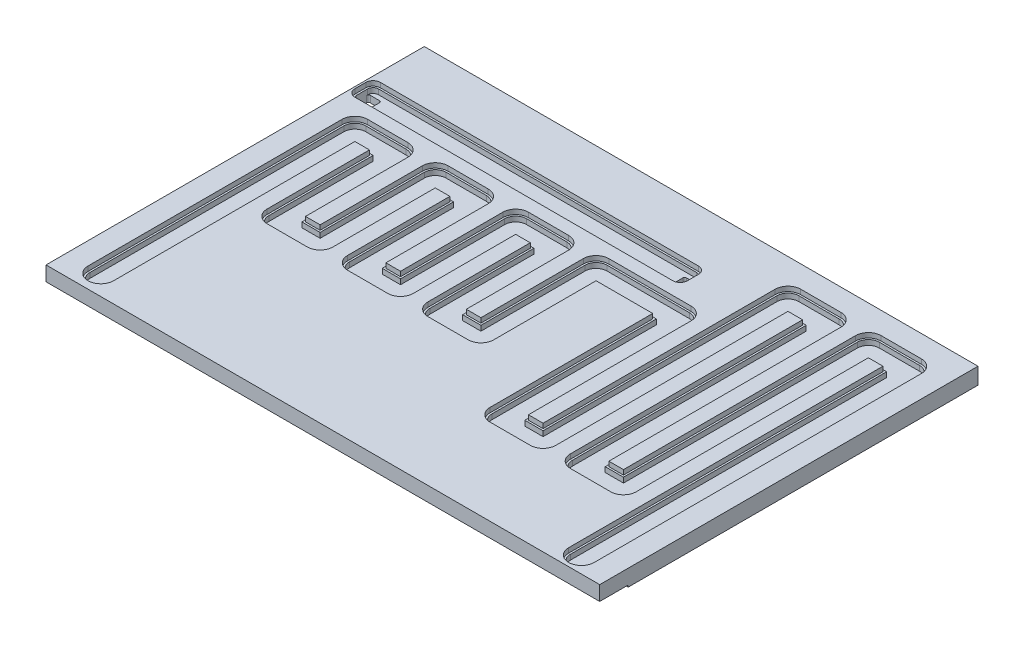
SolidWorks part; units mm, degrees
ref_plane "前视基准面" through (0, 0, 0) normal (0, 0, 1) x (1, 0, 0)
ref_plane "上视基准面" through (0, 0, 0) normal (0, 1, 0) x (1, 0, 0)
ref_plane "右视基准面" through (0, 0, 0) normal (1, 0, 0) x (0, 0, -1)
sketch "草图1" plane through (0, 0, 0) normal (0, 1, 0) x (1, 0, 0)
  line L0 (5, -195) -> (5, -165)
  line L1 (0, 0) -> (1515, 0)
  line L2 (0, 0) -> (0, -1035)
  line L3 (0, -1035) -> (1515, -1035)
  line L4 (1515, 0) -> (1515, -1035)
  line L5 (25, -145) -> (895, -145)
  line L6 (915, -165) -> (915, -195)
  line L7 (895, -215) -> (25, -215)
  line L8 (-125.9274, -180) -> (1036.3031, -180) construction
  line L9 (25, -150) -> (895, -150)
  line L10 (910, -165) -> (910, -195)
  line L11 (895, -210) -> (25, -210)
  line L12 (10, -195) -> (10, -165)
  line L13 (60, -980) -> (60, -285)
  line L14 (40, -197.5) -> (15, -197.5)
  line L15 (45, -192.5) -> (45, -167.5)
  line L16 (40, -162.5) -> (15, -162.5)
  line L17 (10, -192.5) -> (10, -167.5)
  line L18 (45, -197.5) -> (10, -162.5) construction
  line L19 (45, -162.5) -> (10, -197.5) construction
  line L20 (905, -197.5) -> (880, -197.5)
  line L21 (910, -192.5) -> (910, -167.5)
  line L22 (905, -162.5) -> (880, -162.5)
  line L23 (875, -192.5) -> (875, -167.5)
  line L24 (910, -197.5) -> (875, -162.5) construction
  line L25 (910, -162.5) -> (875, -197.5) construction
  line L26 (95, -250) -> (205, -250)
  line L27 (240, -285) -> (240, -565)
  line L28 (240, -565) -> (280, -565)
  line L29 (280, -565) -> (280, -285)
  line L30 (315, -250) -> (425, -250)
  line L31 (460, -285) -> (460, -565)
  line L32 (460, -565) -> (500, -565)
  line L33 (500, -565) -> (500, -285)
  line L34 (535, -250) -> (645, -250)
  line L35 (680, -285) -> (680, -565)
  line L36 (680, -565) -> (720, -565)
  line L37 (720, -565) -> (720, -285)
  line L38 (755, -250) -> (980, -250)
  line L39 (1015, -285) -> (1015, -730)
  line L40 (1015, -730) -> (1055, -730)
  line L41 (1055, -730) -> (1055, -95)
  line L42 (1090, -60) -> (1200, -60)
  line L43 (1235, -95) -> (1235, -730)
  line L44 (1235, -730) -> (1275, -730)
  line L45 (1275, -730) -> (1275, -95)
  line L46 (1310, -60) -> (1420, -60)
  line L47 (1455, -95) -> (1455, -990)
  line L48 (1455, -990) -> (1385, -990) construction
  line L49 (1385, -990) -> (1385, -130)
  line L50 (1385, -130) -> (1345, -130)
  line L51 (1345, -130) -> (1345, -765)
  line L52 (1310, -800) -> (1200, -800)
  line L53 (1165, -765) -> (1165, -130)
  line L54 (1165, -130) -> (1125, -130)
  line L55 (1125, -130) -> (1125, -765)
  line L56 (1090, -800) -> (980, -800)
  line L57 (945, -765) -> (945, -320)
  line L58 (945, -320) -> (790, -320)
  line L59 (790, -320) -> (790, -600)
  line L60 (755, -635) -> (645, -635)
  line L61 (610, -600) -> (610, -320)
  line L62 (610, -320) -> (570, -320)
  line L63 (570, -320) -> (570, -600)
  line L64 (535, -635) -> (425, -635)
  line L65 (390, -600) -> (390, -320)
  line L66 (390, -320) -> (350, -320)
  line L67 (350, -320) -> (350, -600)
  line L68 (315, -635) -> (205, -635)
  line L69 (170, -600) -> (170, -320)
  line L70 (170, -320) -> (130, -320)
  line L71 (130, -320) -> (130, -980)
  line L72 (130, -980) -> (60, -980) construction
  line L73 (1390, -990) -> (1390, -125)
  line L74 (1390, -125) -> (1340, -125)
  line L75 (1340, -125) -> (1340, -765)
  line L76 (1310, -795) -> (1200, -795)
  line L77 (1170, -765) -> (1170, -125)
  line L78 (1170, -125) -> (1120, -125)
  line L79 (1120, -125) -> (1120, -765)
  line L80 (1090, -795) -> (980, -795)
  line L81 (950, -765) -> (950, -315)
  line L82 (950, -315) -> (785, -315)
  line L83 (785, -315) -> (785, -600)
  line L84 (755, -630) -> (645, -630)
  line L85 (615, -600) -> (615, -315)
  line L86 (615, -315) -> (565, -315)
  line L87 (565, -315) -> (565, -600)
  line L88 (535, -630) -> (425, -630)
  line L89 (395, -600) -> (395, -315)
  line L90 (395, -315) -> (345, -315)
  line L91 (345, -315) -> (345, -600)
  line L92 (315, -630) -> (205, -630)
  line L93 (175, -600) -> (175, -315)
  line L94 (175, -315) -> (125, -315)
  line L95 (125, -315) -> (125, -980)
  line L96 (65, -980) -> (65, -285)
  line L97 (95, -255) -> (205, -255)
  line L98 (235, -285) -> (235, -570)
  line L99 (235, -570) -> (285, -570)
  line L100 (285, -570) -> (285, -285)
  line L101 (315, -255) -> (425, -255)
  line L102 (455, -285) -> (455, -570)
  line L103 (455, -570) -> (505, -570)
  line L104 (505, -570) -> (505, -285)
  line L105 (535, -255) -> (645, -255)
  line L106 (675, -285) -> (675, -570)
  line L107 (675, -570) -> (725, -570)
  line L108 (725, -570) -> (725, -285)
  line L109 (755, -255) -> (980, -255)
  line L110 (1010, -285) -> (1010, -735)
  line L111 (1010, -735) -> (1060, -735)
  line L112 (1060, -735) -> (1060, -95)
  line L113 (1090, -65) -> (1200, -65)
  line L114 (1230, -95) -> (1230, -735)
  line L115 (1230, -735) -> (1280, -735)
  line L116 (1280, -735) -> (1280, -95)
  line L117 (1310, -65) -> (1420, -65)
  line L118 (1450, -95) -> (1450, -990)
  arc A0 (5, -195) -> (25, -215) centre (25, -195) ccw
  arc A1 (5, -165) -> (25, -145) centre (25, -165) cw
  arc A2 (915, -195) -> (895, -215) centre (895, -195) cw
  arc A3 (895, -145) -> (915, -165) centre (895, -165) cw
  arc A4 (895, -150) -> (910, -165) centre (895, -165) cw
  arc A5 (910, -195) -> (895, -210) centre (895, -195) cw
  arc A6 (10, -195) -> (25, -210) centre (25, -195) ccw
  arc A7 (10, -165) -> (25, -150) centre (25, -165) cw
  arc A10 (205, -635) -> (170, -600) centre (205, -600) cw
  arc A11 (350, -600) -> (315, -635) centre (315, -600) cw
  arc A12 (425, -635) -> (390, -600) centre (425, -600) cw
  arc A13 (570, -600) -> (535, -635) centre (535, -600) cw
  arc A14 (645, -635) -> (610, -600) centre (645, -600) cw
  arc A15 (790, -600) -> (755, -635) centre (755, -600) cw
  arc A16 (980, -800) -> (945, -765) centre (980, -765) cw
  arc A17 (1125, -765) -> (1090, -800) centre (1090, -765) cw
  arc A18 (1200, -800) -> (1165, -765) centre (1200, -765) cw
  arc A19 (1345, -765) -> (1310, -800) centre (1310, -765) cw
  arc A20 (1420, -60) -> (1455, -95) centre (1420, -95) cw
  arc A21 (1275, -95) -> (1310, -60) centre (1310, -95) cw
  arc A22 (1200, -60) -> (1235, -95) centre (1200, -95) cw
  arc A23 (1055, -95) -> (1090, -60) centre (1090, -95) cw
  arc A24 (980, -250) -> (1015, -285) centre (980, -285) cw
  arc A25 (720, -285) -> (755, -250) centre (755, -285) cw
  arc A26 (645, -250) -> (680, -285) centre (645, -285) cw
  arc A27 (500, -285) -> (535, -250) centre (535, -285) cw
  arc A28 (425, -250) -> (460, -285) centre (425, -285) cw
  arc A29 (280, -285) -> (315, -250) centre (315, -285) cw
  arc A30 (205, -250) -> (240, -285) centre (205, -285) cw
  arc A31 (60, -285) -> (95, -250) centre (95, -285) cw
  arc A32 (1340, -765) -> (1310, -795) centre (1310, -765) cw
  arc A33 (1200, -795) -> (1170, -765) centre (1200, -765) cw
  arc A34 (1120, -765) -> (1090, -795) centre (1090, -765) cw
  arc A35 (980, -795) -> (950, -765) centre (980, -765) cw
  arc A36 (785, -600) -> (755, -630) centre (755, -600) cw
  arc A37 (645, -630) -> (615, -600) centre (645, -600) cw
  arc A38 (565, -600) -> (535, -630) centre (535, -600) cw
  arc A39 (425, -630) -> (395, -600) centre (425, -600) cw
  arc A40 (345, -600) -> (315, -630) centre (315, -600) cw
  arc A41 (205, -630) -> (175, -600) centre (205, -600) cw
  arc A42 (65, -285) -> (95, -255) centre (95, -285) cw
  arc A43 (205, -255) -> (235, -285) centre (205, -285) cw
  arc A44 (285, -285) -> (315, -255) centre (315, -285) cw
  arc A45 (425, -255) -> (455, -285) centre (425, -285) cw
  arc A46 (505, -285) -> (535, -255) centre (535, -285) cw
  arc A47 (645, -255) -> (675, -285) centre (645, -285) cw
  arc A48 (725, -285) -> (755, -255) centre (755, -285) cw
  arc A49 (980, -255) -> (1010, -285) centre (980, -285) cw
  arc A50 (1060, -95) -> (1090, -65) centre (1090, -95) cw
  arc A51 (1200, -65) -> (1230, -95) centre (1200, -95) cw
  arc A52 (1280, -95) -> (1310, -65) centre (1310, -95) cw
  arc A53 (1420, -65) -> (1450, -95) centre (1420, -95) cw
  arc A54 (60, -980) -> (130, -980) centre (95, -980) ccw
  arc A55 (1390, -990) -> (1450, -990) centre (1420, -990) ccw
  arc A56 (910, -167.5) -> (905, -162.5) centre (905, -167.5) ccw
  arc A57 (905, -197.5) -> (910, -192.5) centre (905, -192.5) ccw
  arc A58 (880, -197.5) -> (875, -192.5) centre (880, -192.5) cw
  arc A59 (880, -162.5) -> (875, -167.5) centre (880, -167.5) ccw
  arc A60 (15, -162.5) -> (10, -167.5) centre (15, -167.5) ccw
  arc A61 (15, -197.5) -> (10, -192.5) centre (15, -192.5) cw
  arc A62 (40, -197.5) -> (45, -192.5) centre (40, -192.5) ccw
  arc A63 (45, -167.5) -> (40, -162.5) centre (40, -167.5) ccw
  arc A65 (1385, -990) -> (1455, -990) centre (1420, -990) ccw
  arc A66 (65, -980) -> (125, -980) centre (95, -980) ccw
  point P31 (27.5, -180)
  point P36 (892.5, -180)
  point P89 (350, -460)
  point P90 (790, -460)
  point P91 (1035, -800)
  point P93 (280, -425)
  point P94 (1365, -60)
  point P95 (95, -980)
  point P96 (1420, -990)
  dimension "D7" = 20
  dimension "D51" = 35
  dimension "D55" = 5
  dimension "D54" = 35
  dimension "D1" = 1515
  dimension "D2" = 1035
  dimension "D3" = 180
  dimension "D4" = 70
  dimension "D5" = 5
  dimension "D6" = 910
  dimension "D9" = 35
  dimension "D10" = 35
  dimension "D11" = 35
  dimension "D12" = 35
  dimension "D13" = 865
  dimension "D14" = 60
  dimension "D15" = 70
  dimension "D16" = 70
  dimension "D17" = 70
  dimension "D18" = 70
  dimension "D19" = 70
  dimension "D20" = 70
  dimension "D21" = 70
  dimension "D22" = 70
  dimension "D23" = 70
  dimension "D24" = 70
  dimension "D25" = 70
  dimension "D26" = 70
  dimension "D27" = 400
  dimension "D28" = 70
  dimension "D29" = 70
  dimension "D30" = 70
  dimension "D31" = 70
  dimension "D32" = 70
  dimension "D33" = 245
  dimension "D34" = 70
  dimension "D35" = 70
  dimension "D36" = 295
  dimension "D37" = 40
  dimension "D38" = 40
  dimension "D39" = 40
  dimension "D40" = 40
  dimension "D41" = 40
  dimension "D42" = 40
  dimension "D43" = 40
  dimension "D44" = 40
  dimension "D45" = 40
  dimension "D46" = 40
  dimension "D47" = 235
  dimension "D48" = 975
  dimension "D49" = 55
  dimension "D50" = 45
  dimension "D52" = 5
  dimension "D8" = 5
extrude "凸台-拉伸1" add sketch "草图1" against normal blind 45 contours L3 L4 L1 L2
extrude "切除-拉伸1" cut sketch "草图1<3>" against normal blind 13 contours L7 A0 L0 A1 L5 A3 L6 A2
sketch "草图1<3>" plane through (0, 0, 0) normal (0, 1, 0) x (1, 0, 0) same geometry as "草图1"
extrude "切除-拉伸2" cut sketch "草图1<5>" against normal blind 27 contours L9 A4 L10 A5 L11 A6 L12 A7
sketch "草图1<5>" plane through (0, 0, 0) normal (0, 1, 0) x (1, 0, 0) same geometry as "草图1"
extrude "切除-拉伸3" cut sketch "草图1<6>" against normal blind 45 contours L15 A63 L16 A60 L17 A61 L14 A62 | L23 A59 L22 A56 L21 A57 L20 A58
sketch "草图1<6>" plane through (0, 0, 0) normal (0, 1, 0) x (1, 0, 0) same geometry as "草图1"
extrude "切除-拉伸5" cut sketch "草图1<9>" against normal blind 13 contours L71 A54 L13 A31 L26 A30 L27 L28 L29 A29 L30 A28 L31 L32 L33 A27 L34 A26 L35 L36 L37 A25 L38 A24 L39 L40 L41 A23 L42 A22 L43 L44 L45 A21 L46 A20 L47 A65 L49 L50 L51 A19 L52 A18 L53 L54 L55 A17 L56 A16 L57 L58 L59 A15 L60 A14 L61 L62 L63 A13 L64 A12 L65 L66 L67 A11 L68 A10 L69 L70
sketch "草图1<9>" plane through (0, 0, 0) normal (0, 1, 0) x (1, 0, 0) same geometry as "草图1"
extrude "切除-拉伸6" cut sketch "草图1<10>" against normal blind 27 contours L73 L74 L75 A32 L76 A33 L77 L78 L79 A34 L80 A35 L81 L82 L83 A36 L84 A37 L85 L86 L87 A38 L88 A39 L89 L90 L91 A40 L92 A41 L93 L94 L95 A66 L96 A42 L97 A43 L98 L99 L100 A44 L101 A45 L102 L103 L104 A46 L105 A47 L106 L107 L108 A48 L109 A49 L110 L111 L112 A50 L113 A51 L114 L115 L116 A52 L117 A53 L118 A55
sketch "草图1<10>" plane through (0, 0, 0) normal (0, 1, 0) x (1, 0, 0) same geometry as "草图1"
sketch "草图3" plane through (0, 0, 0) normal (0, 1, 0) x (1, 0, 0)
  line L0 (0, -1035) -> (1515, -1035) construction
  circle A0 centre (95, -990) radius 10.25
  circle A1 centre (1420, -1007.5) radius 10.25
  dimension "D1" = 20.5
  dimension "D2" = 45
  dimension "D3" = 27.5
extrude "切除-拉伸7" cut sketch "草图3" against normal blind 45
sketch "草图5" plane through (0, -45, 0) normal (0, -1, 0) x (1, 0, 0)
  line L10 (757.5, 0) -> (757.5, 1207.0434) construction
  line L11 (0, 0) -> (1515, 0) construction
  line L12 (0, 932) -> (0, 1035)
  line L13 (0, 1035) -> (1515, 1035)
  line L14 (1515, 1035) -> (1515, 957)
  line L15 (885, 957) -> (1515, 957)
  line L16 (865, 932) -> (865, 937)
  line L17 (865, 937) -> (885, 957)
  line L18 (0, 932) -> (865, 932)
  line L19 (0, 1035) -> (1515, 1035) construction
  dimension "D1" = 865
  dimension "D2" = 5
  dimension "D3" = 20
  dimension "D4" = 103
  dimension "D5" = 78
extrude "切除-拉伸8" cut sketch "草图5" against normal blind 5
sketch "草图6" plane through (0, -45, 0) normal (0, -1, 0) x (1, 0, 0)
  line L1 (0, 0) -> (1515, 0) construction
  line L2 (757.5, 0) -> (757.5, 1247.6154) construction
  line L3 (1515, 0) -> (1515, 957) construction
  circle A16 centre (710, 875) radius 5.25
  circle A17 centre (605, 875) radius 5.25
  circle A18 centre (500, 875) radius 5.25
  circle A19 centre (395, 875) radius 5.25
  circle A20 centre (290, 875) radius 5.25
  circle A21 centre (185, 875) radius 5.25
  circle A22 centre (150, 673) radius 5.25
  circle A23 centre (246, 673) radius 5.25
  circle A24 centre (659, 673) radius 5.25
  circle A25 centre (755, 673) radius 5.25
  circle A26 centre (325, 40) radius 5.25
  circle A27 centre (385, 40) radius 5.25
  circle A28 centre (520, 40) radius 5.25
  circle A29 centre (580, 40) radius 5.25
  circle A30 centre (1045, 35) radius 8.75
  circle A31 centre (1395, 35) radius 8.75
  dimension "D8" = 60
  dimension "D9" = 633
  dimension "D20" = 10.5
  dimension "D21" = 17.5
  dimension "D22" = 17.5
  dimension "D1" = 120
  dimension "D2" = 350
  dimension "D3" = 35
  dimension "D4" = 5
  dimension "D5" = 465
  dimension "D6" = 60
  dimension "D7" = 135
  dimension "D10" = 139
  dimension "D11" = 202
  dimension "D12" = 96
  dimension "D13" = 413
  dimension "D14" = 96
  dimension "D15" = 105
  dimension "D16" = 105
  dimension "D17" = 105
  dimension "D18" = 105
  dimension "D19" = 105
  dimension "D23" = 35
extrude "切除-拉伸9" cut sketch "草图6" against normal blind 25
extrude "切除-拉伸10" cut sketch "草图6<4>" against normal blind 35 contours A31 | A30
sketch "草图6<4>" plane through (0, -45, 0) normal (0, -1, 0) x (1, 0, 0) same geometry as "草图6"
